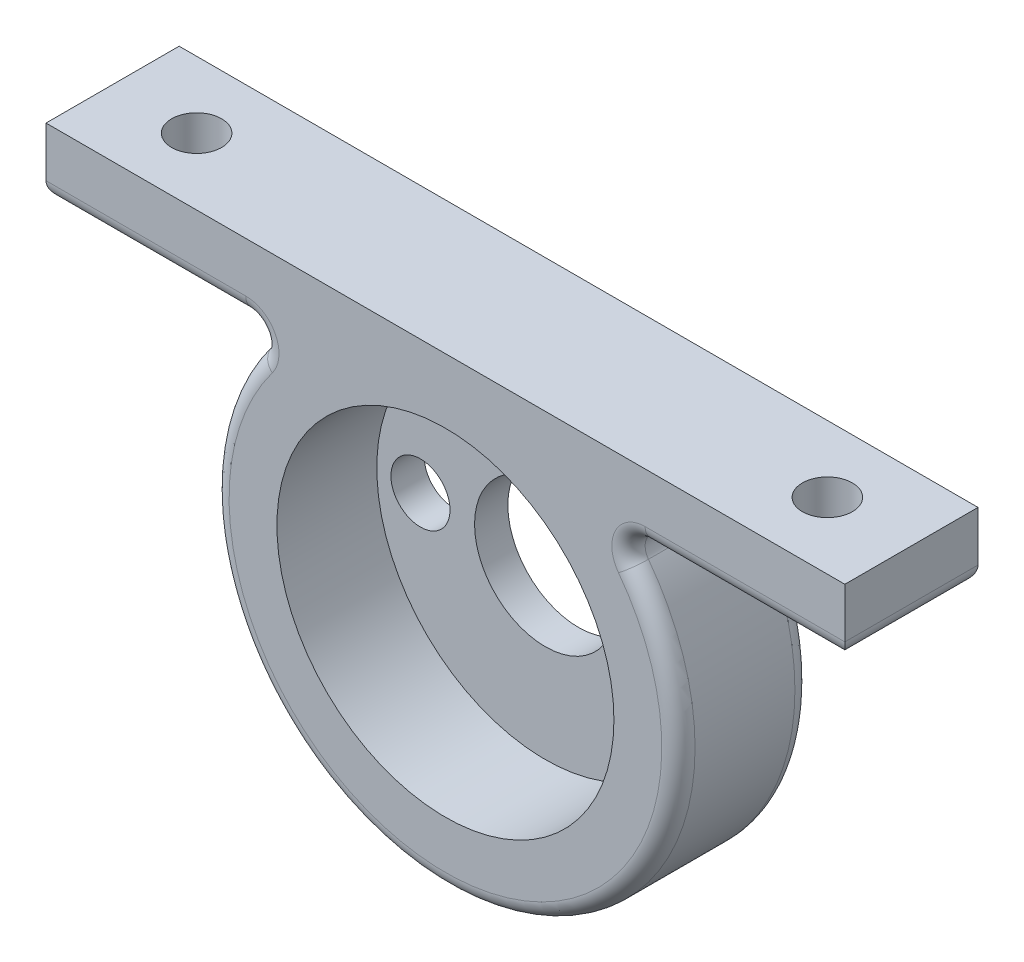
SolidWorks part; units mm, degrees
material "ABS"
ref_plane "Alzado" through (0, 0, 0) normal (0, 0, 1) x (1, 0, 0)
ref_plane "Planta" through (0, 0, 0) normal (0, 1, 0) x (1, 0, 0)
ref_plane "Vista lateral" through (0, 0, 0) normal (1, 0, 0) x (0, 0, -1)
sketch "Croquis1" plane through (0, 0, 0) normal (0, 0, 1) x (1, 0, 0)
  line L0 (0, 14) -> (24, 14)
  line L1 (0, 14) -> (-24, 14)
  line L2 (-24, 14) -> (-24, 10)
  line L3 (-24, 10) -> (-9.798, 10)
  line L4 (24, 14) -> (24, 10)
  line L5 (24, 10) -> (9.798, 10)
  arc A1 (-9.798, 10) -> (9.798, 10) centre (0, 0) ccw
  dimension "D1" = 14
  dimension "D2" = 14
  dimension "D3" = 48
  dimension "D5" = 4
  dimension "D6" = 4
  dimension "D7" = 24
extrude "Saliente-Extruir1" add sketch "Croquis1" along normal blind 8
fillet "Redondeo1" radius 1 10 edges at (-16.899, 10, 8) (-16.899, 10, 0) (16.899, 10, 8) (16.899, 10, 0) (-9.798, 10, 4) (0, -14, 8) (9.798, 10, 4) (0, -14, 0) (24, 10, 4) (-24, 10, 4)
sketch "Croquis2" plane through (0, 10, 0) normal (0, -1, 0) x (1, 0, 0)
  line L0 (23, 1) -> (23, 7) construction
  line L2 (12, 1) -> (23, 1) construction
  line L4 (-23, 1) -> (-12, 1) construction
  line L5 (-23, 7) -> (-23, 1) construction
  circle A0 centre (-18.9495, 4) radius 1.5
  circle A1 centre (18.9495, 4) radius 1.5
  dimension "D1" = 3
  dimension "D2" = 3
  dimension "D3" = 4.0505
  dimension "D4" = 3
  dimension "D5" = 3
  dimension "D6" = 4.0505
extrude "Cortar-Extruir1" cut sketch "Croquis2" against normal through all
sketch "Croquis3" plane through (0, 0, 8) normal (0, 0, 1) x (1, 0, 0)
  circle A0 centre (0, 0) radius 10.125
  dimension "D1" = 20.25
extrude "Cortar-Extruir2" cut sketch "Croquis3" against normal blind 6
sketch "Croquis4" plane through (0, 0, 0) normal (0, 0, -1) x (-1, 0, 0)
  line L0 (-24, 14) -> (24, 14) construction
  circle A0 centre (0, 0) radius 4.25
  circle A1 centre (7.5, 0) radius 1.775
  circle A2 centre (-7.5, 0) radius 1.775
  dimension "D1" = 8.5
  dimension "D2" = 7.5
  dimension "D3" = 7.5
  dimension "D4" = 3.55
  dimension "D5" = 3.55
  dimension "D6" = 14
  dimension "D7" = 14
extrude "Cortar-Extruir3" cut sketch "Croquis4" against normal through all
